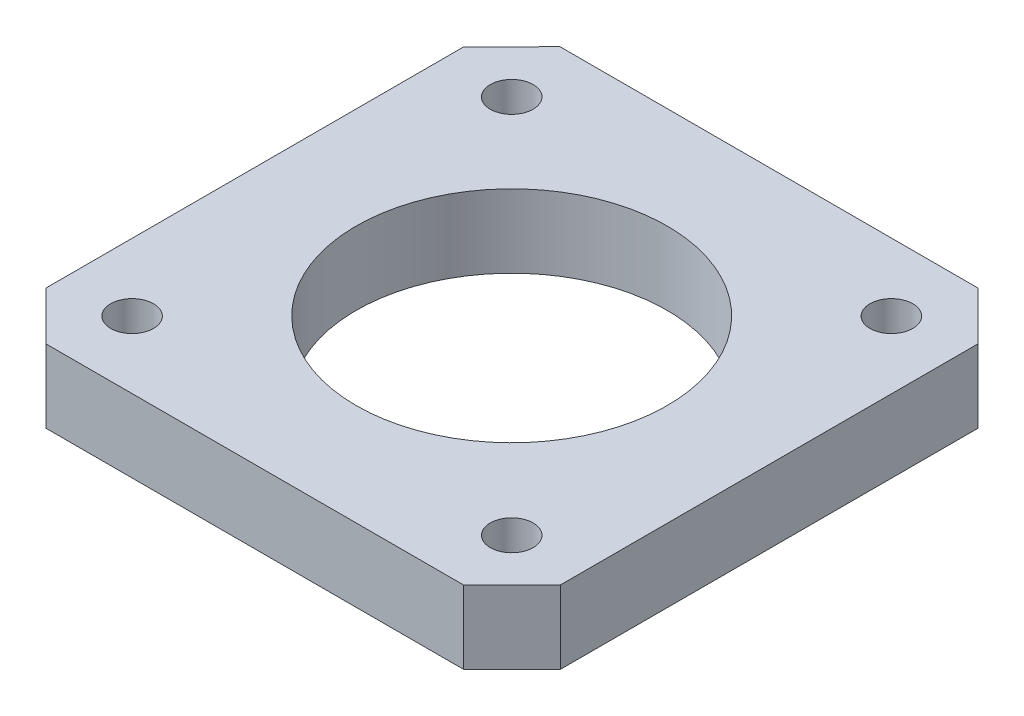
SolidWorks part; units mm, degrees
ref_plane "Front Plane" through (0, 0, 0) normal (0, 0, 1) x (1, 0, 0)
ref_plane "Top Plane" through (0, 0, 0) normal (0, 1, 0) x (1, 0, 0)
ref_plane "Right Plane" through (0, 0, 0) normal (1, 0, 0) x (0, 0, -1)
sketch "Sketch1" plane through (0, 0, 0) normal (0, 1, 0) x (1, 0, 0)
  line L0 (0, 38.0077) -> (3.9098, 42)
  line L1 (0, 0) -> (42, 0)
  line L2 (0, 0) -> (0, 42)
  line L3 (0, 42) -> (42, 42)
  line L4 (42, 0) -> (42, 42)
  line L5 (38.0433, 42) -> (42, 38.0541)
  line L6 (0, 0) -> (3.9512, 0) construction
  line L7 (0, 0) -> (0, 3.9512) construction
  line L8 (0, 3.9512) -> (3.9512, 0)
  line L9 (42, 0) -> (42, 3.9512) construction
  line L10 (42, 0) -> (38.0488, 0) construction
  line L11 (38.0488, 0) -> (42, 3.9512)
extrude "Boss-Extrude1" add sketch "Sketch1" along normal blind 5.969 contours L1 L11 L4 L5 L3 L0 L2 L8 region at (21.0001, 0, -21.0001)
sketch "Sketch2" plane through (0, 5.969, 0) normal (0, 1, 0) x (1, 0, 0)
  line L0 (0, 20.9794) -> (42, 20.9794) construction
  line L1 (0, 3.9512) -> (0, 38.0077) construction
  line L2 (42, 3.9512) -> (42, 38.0541) construction
  line L3 (20.9766, 42) -> (20.9766, 0) construction
  line L4 (3.9098, 42) -> (38.0433, 42) construction
  line L5 (3.9512, 0) -> (38.0488, 0) construction
  line L6 (36.5, 20.9794) -> (5.5, 20.9794) construction
  line L7 (5.5, 5.4794) -> (5.5, 36.4794) construction
  line L8 (36.5, 36.4794) -> (36.5, 5.4794) construction
  circle A0 centre (5.5, 36.4794) radius 1.75
  circle A1 centre (36.5, 36.4794) radius 1.75
  circle A2 centre (36.5, 5.4794) radius 1.75
  circle A3 centre (5.5, 5.4794) radius 1.75
  point P15 (21, 20.9794)
  point P17 (5.5, 20.9794)
  point P21 (36.5, 20.9794)
extrude "Cut-Extrude1" cut sketch "Sketch2" against normal blind 5.969
sketch "Sketch3" plane through (0, 5.969, 0) normal (0, 1, 0) x (1, 0, 0)
  line L0 (20.9766, 42) -> (20.9766, 0) construction
  line L1 (3.9098, 42) -> (38.0433, 42) construction
  line L2 (3.9512, 0) -> (38.0488, 0) construction
  line L3 (0, 20.9794) -> (42, 20.9794) construction
  line L4 (0, 3.9512) -> (0, 38.0077) construction
  line L5 (42, 3.9512) -> (42, 38.0541) construction
  circle A0 centre (20.9766, 21) radius 12.7
extrude "Cut-Extrude2" cut sketch "Sketch3" against normal blind 16.51
